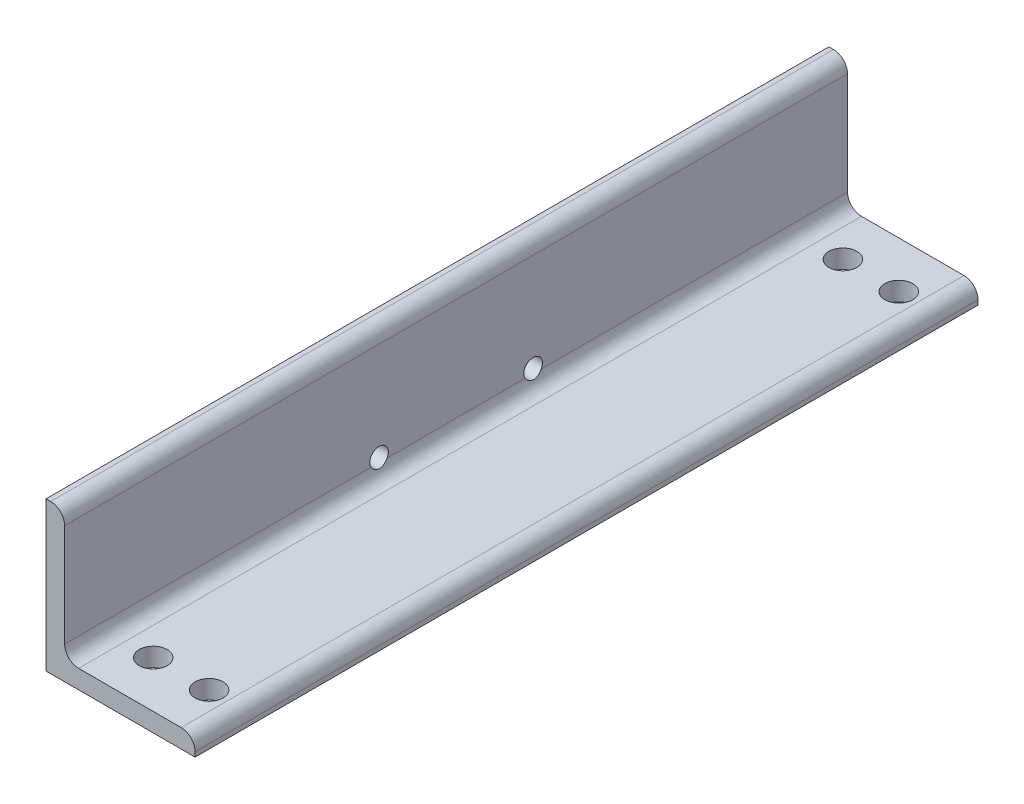
SolidWorks part; units mm, degrees
ref_plane "Front Plane" through (0, 0, 0) normal (0, 0, 1) x (1, 0, 0)
ref_plane "Top Plane" through (0, 0, 0) normal (0, 1, 0) x (1, 0, 0)
ref_plane "Right Plane" through (0, 0, 0) normal (1, 0, 0) x (0, 0, -1)
sketch "Sketch1" plane through (0, 0, 0) normal (0, 0, 1) x (1, 0, 0)
  line L0 (0, 0) -> (0, 101.6)
  line L1 (0, 101.6) -> (3.1801, 101.6)
  line L2 (12.7, 92.0801) -> (12.7, 22.225)
  line L3 (22.225, 12.7) -> (92.0801, 12.7)
  line L4 (101.6, 3.1801) -> (101.6, 0)
  line L5 (101.6, 0) -> (0, 0)
  arc A0 (101.6, 3.1801) -> (92.0801, 12.7) centre (92.0801, 3.1801) ccw
  arc A1 (3.1801, 101.6) -> (12.7, 92.0801) centre (3.1801, 92.0801) cw
  arc A2 (22.225, 12.7) -> (12.7, 22.225) centre (22.225, 22.225) cw
  circle A3 centre (0, 0) radius 9.525 construction
  dimension "D2" = 3.1801
  dimension "Radius_1" = 9.525
  dimension "Radius_2" = 9.525
  dimension "D1" = 12.7
  dimension "V_leg" = 101.6
  dimension "H_leg" = 101.6
  dimension "Thickness" = 12.7
  dimension "Flat_wid" = 3.1801
extrude "Boss-Extrude1" add sketch "Sketch1" along normal mid plane 533.4
sketch "Sketch3" plane through (25.4, 12.7, 0) normal (0, 1, 0) x (0, 0, -1)
  line L0 (266.7, -34.925) -> (266.7, 3.175) construction
  line L1 (-266.7, 25.4) -> (266.7, 25.4) construction
  line L2 (266.7, -34.925) -> (-260.35, -34.925) construction
  line L5 (0, 12.7) -> (0, 20.3926) construction
  line L6 (-266.7, 12.7) -> (266.7, 12.7) construction
  circle A0 centre (234.95, -15.875) radius 9.525
  circle A1 centre (-234.95, -15.875) radius 9.525
  circle A2 centre (-234.95, -53.975) radius 9.525
  circle A3 centre (234.95, -53.975) radius 9.525
  dimension "D1" = 19.05
  dimension "D3" = 19.05
  dimension "D2" = 234.95
  dimension "D4" = 41.275
extrude "Cut-Extrude1" cut sketch "Sketch3" against normal up to next
sketch "Sketch4" plane through (0, 0, 0) normal (-1, 0, 0) x (0, 0, 1)
  line L0 (-52.4891, 25.4) -> (52.4891, 25.4) construction
  line L1 (0, 25.4) -> (0, 0) construction
  line L2 (266.7, 0) -> (-266.7, 0) construction
  circle A0 centre (-52.4891, 25.4) radius 6.35
  circle A1 centre (52.4891, 25.4) radius 6.35
  dimension "D1" = 12.7
  dimension "D2" = 104.9782
  dimension "D3" = 25.4
extrude "Cut-Extrude2" cut sketch "Sketch4" against normal up to next
